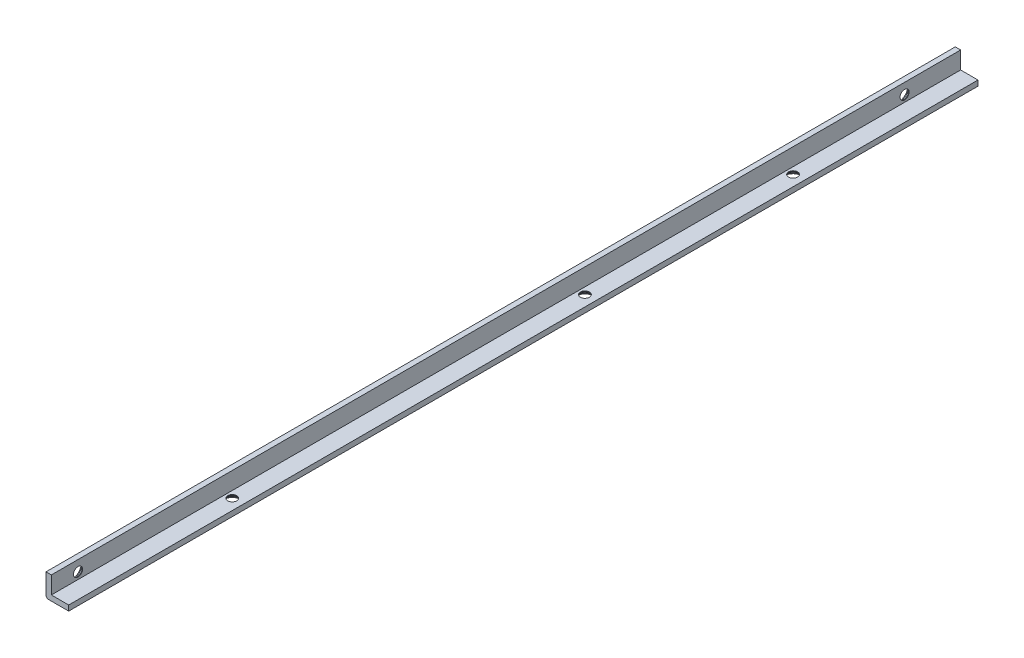
SolidWorks part; units mm, degrees
material "7075-T6 (SN)"
ref_plane "Front Plane" through (0, 0, 0) normal (0, 0, 1) x (1, 0, 0)
ref_plane "Top Plane" through (0, 0, 0) normal (0, 1, 0) x (1, 0, 0)
ref_plane "Right Plane" through (0, 0, 0) normal (1, 0, 0) x (0, 0, -1)
sketch "Sketch1" plane through (0, 0, 0) normal (0, 0, 1) x (1, 0, 0)
  line L0 (0, 0) -> (-8.5, 0)
  line L1 (-8.5, 0) -> (-8.5, 8.5)
  line L2 (-8.5, 8.5) -> (-6.5, 8.5)
  line L3 (-6.5, 8.5) -> (-6.5, 2)
  line L4 (-6.5, 2) -> (0, 2)
  line L5 (0, 2) -> (0, 0)
  dimension "D1" = 2
  dimension "D2" = 2
  dimension "D3" = 8.5
  dimension "D4" = 8.5
extrude "Boss-Extrude1" add sketch "Sketch1" along normal blind 340.5
fillet "Fillet1" radius 1 1 edges at (-8.5, 0, 170.25)
ref_plane "Plane1" through (0, 0, 170.25) normal (0, 0, 1) x (1, 0, 0)
sketch "Sketch2" plane through (-6.5, 0, 0) normal (1, 0, 0) x (0, 0, -1)
  point P0 (-330.5, 4.5)
  point P1 (-21, 4.5)
  point P3 (-21, 4.5)
sketch "Sketch3" plane through (0, 2, 0) normal (0, 1, 0) x (1, 0, 0)
  point P0 (-4, -275.25)
  point P1 (-4, -143.2)
  point P3 (-4, -65.25)
sketch "Sketch5" plane through (-8.5, 0, 0) normal (-1, 0, 0) x (0, 0, 1)
  point P0 (21, 4.5)
  point P2 (330.5, 4.5)
sketch "Sketch6" plane through (0, 0, 0) normal (0, -1, 0) x (1, 0, 0)
  point P0 (-4, 143.2)
  point P2 (-4, 275.25)
  point P4 (-4, 65.25)
hole_wizard "CSK for M3 Countersunk Flat Head Screw1" positions "3DSketch2" profile "Sketch7" countersink size "M3" standard "ISO"
sketch3d "3DSketch2"
  point P0 (-8.5, 4.5, 21)
  point P3 (-4, 0, 65.25)
  point P6 (-4, 0, 143.2)
  point P9 (-4, 0, 275.25)
  point P12 (-8.5, 4.5, 330.5)
sketch "Sketch7" plane through (-8.5, 4.5, 21) normal (0, 1, 0) x (0, 0, 1)
  line L0 (0, 0) -> (0, 10.5215)
  line L1 (0, 10.5215) -> (1.7, 9.5)
  line L2 (1.7, 9.5) -> (1.7, 1.75)
  line L3 (1.7, 1.75) -> (3.15, 0.3)
  line L4 (3.15, 0.3) -> (3.15, 0)
  line L6 (3.15, 0) -> (0, 0)
  line L7 (-1.7, 1.75) -> (-3.15, 0.3) construction
  line L10 (0, 10.5215) -> (-1.7, 9.5) construction
  line L11 (0, -6.35) -> (0, 107.95) construction
  dimension "Hole Dia." = 3.4
  dimension "Hole Depth" = 9.5
  dimension "C'Sink Dia." = 6.3
  dimension "C'Sink Angle" = 90
  dimension "Drill Angle" = 118
  dimension "Head Clearance" = 0.3
equation "\"thickness\"= 2mm"
equation "\"D1@Sketch1\"=\"thickness\""
equation "\"D2@Sketch1\"=\"D1@Sketch1\""
equation "\"D4@Sketch1\"=\"D3@Sketch1\""
